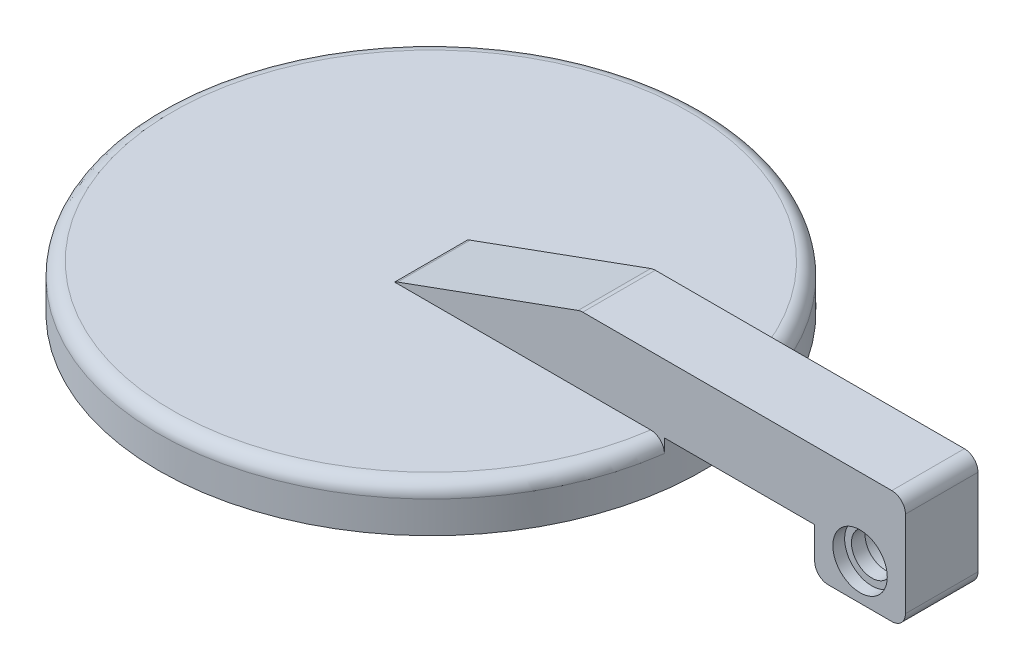
SolidWorks part; units mm, degrees
ref_plane "Front Plane" through (0, 0, 0) normal (0, 0, 1) x (1, 0, 0)
ref_plane "Top Plane" through (0, 0, 0) normal (0, 1, 0) x (1, 0, 0)
ref_plane "Right Plane" through (0, 0, 0) normal (1, 0, 0) x (0, 0, -1)
sketch "Sketch2" plane through (0, 0, 0) normal (0, 0, 1) x (1, 0, 0)
  line L7 (0, 0) -> (30, 0)
  line L8 (0, 0) -> (0, 5)
  line L9 (0, 5) -> (30, 5)
  line L10 (30, 0) -> (30, 5)
  dimension "D1" = 5
  dimension "D2" = 30
revolve "Revolve1" add sketch "Sketch2" angle 360 about L8
sketch "Sketch3" plane through (0, 5, 0) normal (0, 1, 0) x (1, 0, 0)
  line L0 (0, -10) -> (0, 10) construction
  line L1 (0, 10) -> (35, 10)
  line L2 (35, 10) -> (35, 6)
  line L3 (35, 6) -> (0, 6)
  line L4 (0, 10) -> (0, 6)
  line L5 (0, -10) -> (35, -10)
  line L6 (35, -10) -> (35, -6)
  line L7 (35, -6) -> (0, -6)
  line L8 (0, -6) -> (0, -10)
  line L9 (0, 4) -> (0, -4)
  line L10 (0, 4) -> (56.3, 4)
  line L11 (0, -4) -> (56.3, -4)
  line L12 (56.3, -4) -> (56.3, 4)
  point P4 (0, 0)
  point P13 (0, 0)
  circle M1 centre (0, 0) radius 30
  dimension "D1" = 20
  dimension "D2" = 35
  dimension "D3" = 4
  dimension "0.7" = 8
  dimension "D5" = 56.3
extrude "Boss-Extrude1" add sketch "Sketch3" along normal blind 7.5 contours L9 L11 L10 M1 | L11 L12 L10 M1 region at (14.9555, 5, 0) region at (43.1053, 5, 0)
sketch "Sketch4" plane through (0, 0, 0) normal (0, 0, 1) x (1, 0, 0)
  line L5 (35, 8.75) -> (37.8, 8.75) construction
  line L7 (56.3, 8.75) -> (37.8, 8.75) construction
  line L8 (56.3, 12.5) -> (56.3, 5) construction
  line L10 (-0.1339, 5) -> (20.4721, 12.5)
  line L11 (29.7321, 5) -> (-30, 5) construction
  line L12 (0, 12.5) -> (56.3, 12.5) construction
  line L13 (0, 5) -> (29.7321, 5) construction
  line L14 (20.4721, 12.5) -> (0, 12.5)
  line L15 (0, 12.5) -> (-0.1339, 5)
  circle A0 centre (37.8, 8.75) radius 2
  dimension "D3" = 4
  dimension "D1" = 20
  dimension "D2" = 18.5
extrude "Cut-Extrude1" cut sketch "Sketch4" against normal mid plane 30 contours L14 L15 L10
sketch "Sketch6" plane through (0, 5, 0) normal (0, -1, 0) x (1, 0, 0)
  line L6 (56.3, 4) -> (46.3, 4)
  line L7 (56.3, 4) -> (56.3, -4) construction
  line L8 (29.7321, 4) -> (56.3, 4) construction
  line L9 (46.3, 4) -> (46.3, -4)
  line L10 (29.7321, -4) -> (56.3, -4) construction
  line L11 (46.3, -4) -> (56.3, -4)
  line L12 (56.3, -4) -> (56.3, 4)
  dimension "D1" = 10
extrude "Boss-Extrude2" add sketch "Sketch6" along normal blind 5
sketch "Sketch7" plane through (0, 0, 4) normal (0, 0, 1) x (1, 0, 0)
  line L0 (51.3, 4) -> (51.3, 0) construction
  line L2 (56.3, 0) -> (46.3, 0) construction
  circle A0 centre (51.3, 4) radius 3
  dimension "D2" = 6
  dimension "D1" = 4
extrude "Cut-Extrude2" cut sketch "Sketch7" against normal blind 10
fillet "Fillet2" radius 1.5 6 edges at (46.3, 0, 0) (56.3, 0, 0) (56.3, 12.5, 0) (20.4721, 12.5, 0) (0, 5.0487, 0) (-30, 5, 0)
sketch "Sketch9" plane through (0, 0, -4) normal (0, 0, -1) x (-1, 0, 0)
  circle A0 centre (-51.3, 4) radius 3
  circle A1 centre (-51.3, 4) radius 4
  dimension "D1" = 6
  dimension "D2" = 8
sketch "Sketch10" plane through (0, 0, 4) normal (0, 0, 1) x (1, 0, 0)
  circle A0 centre (51.3, 4) radius 3.25
  circle A1 centre (51.3, 4) radius 2.25
  dimension "D1" = 6.5
  dimension "D2" = 4.5
extrude "Boss-Extrude4" add sketch "Sketch10" along normal blind 1.5 from offset 2.8 offset against normal yes
sketch "Sketch11" plane through (0, 0, 1.2) normal (0, 0, -1) x (-1, 0, 0)
  circle A0 centre (-51.3, 4) radius 2.6
  circle A1 centre (-51.3, 4) radius 3
  dimension "D1" = 5.2
  dimension "D2" = 6
extrude "Boss-Extrude5" add sketch "Sketch11" along normal blind 5.2
sketch "Sketch12" plane through (0, 0, 0) normal (0, -1, 0) x (1, 0, 0)
  line L0 (0, 30) -> (0, 25.5) construction
  circle A0 centre (0, 0) radius 30 construction
  circle A1 centre (0, 27.75) radius 1.5
  circle A2 centre (19.6222, 19.6222) radius 1.5
  circle A3 centre (27.75, 0) radius 1.5
  circle A4 centre (19.6222, -19.6222) radius 1.5
  circle A5 centre (0, -27.75) radius 1.5
  circle A6 centre (-19.6222, -19.6222) radius 1.5
  circle A7 centre (-27.75, 0) radius 1.5
  circle A8 centre (-19.6222, 19.6222) radius 1.5
  point P24 (0, 0)
  dimension "D2" = 3
  dimension "D1" = 4.5
  dimension "D3" = 8
extrude "Cut-Extrude3" cut sketch "Sketch12" against normal blind 0.5
sketch "Sketch13" plane through (0, 0, -4) normal (0, 0, -1) x (-1, 0, 0)
  circle A0 centre (-51.3, 4) radius 3
  dimension "D1" = 6
extrude "Cut-Extrude4" cut sketch "Sketch13" against normal blind 5.2
